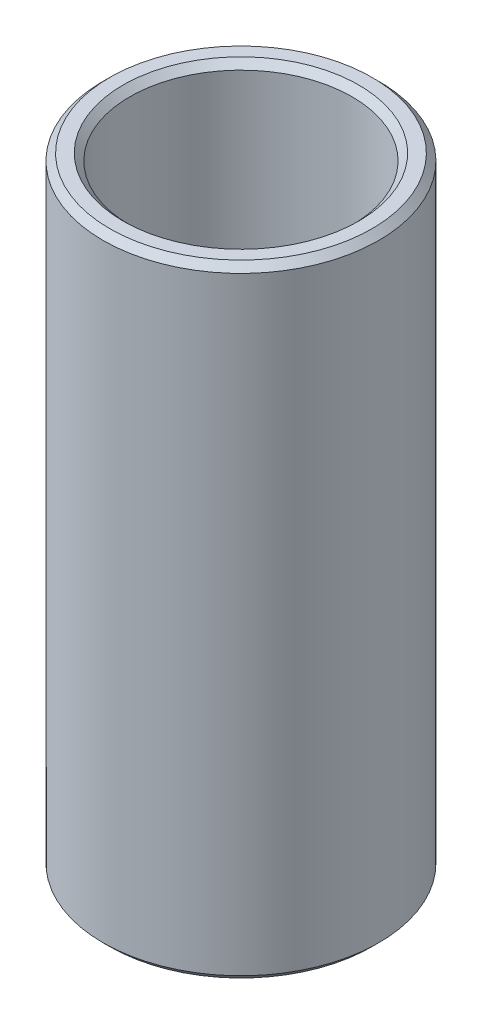
SolidWorks part; units mm, degrees
ref_plane "Front Plane" through (0, 0, 0) normal (0, 0, 1) x (1, 0, 0)
ref_plane "Top Plane" through (0, 0, 0) normal (0, 1, 0) x (1, 0, 0)
ref_plane "Right Plane" through (0, 0, 0) normal (1, 0, 0) x (0, 0, -1)
sketch "Sketch1" plane through (0, 0, 0) normal (0, 1, 0) x (1, 0, 0)
  circle A0 centre (0, 0) radius 45
  dimension "SLEEVE_OD" = 90
extrude "Boss-Extrude1" add sketch "Sketch1" along normal blind 202.9358
sketch "Sketch2" plane through (0, 0, 0) normal (0, 1, 0) x (1, 0, 0)
  circle A0 centre (0, 0) radius 36.2688
  dimension "BORE_D" = 72.5376
extrude "Cut-Extrude1" cut sketch "Sketch2" along normal through all
chamfer "Chamfer1" distance 2.2073 angle 45 4 edges at (0, 202.9358, 36.2688) (0, 0, 36.2688) (0, 0, 45) (0, 202.9358, 45)
